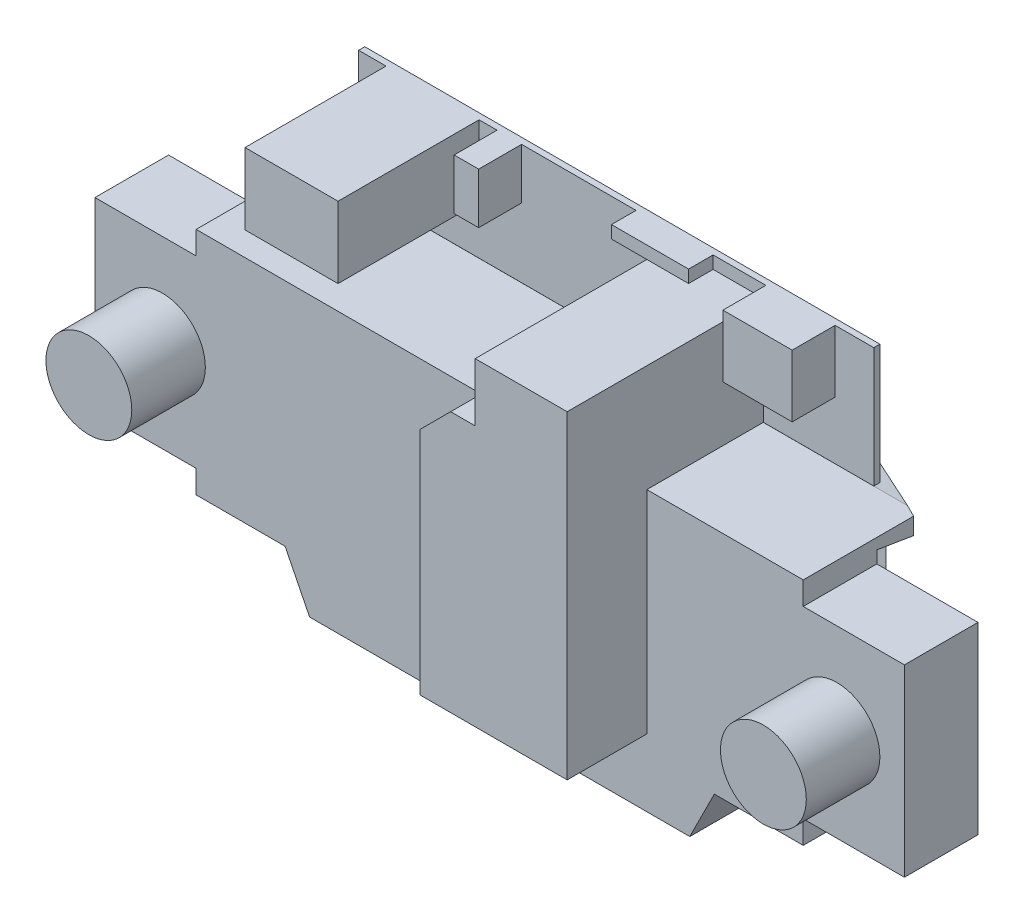
SolidWorks part; units mm, degrees
ref_plane "Front Plane" through (0, 0, 0) normal (0, 0, 1) x (1, 0, 0)
ref_plane "Top Plane" through (0, 0, 0) normal (0, 1, 0) x (1, 0, 0)
ref_plane "Right Plane" through (0, 0, 0) normal (1, 0, 0) x (0, 0, -1)
sketch "Sketch1" plane through (0, 0, 0) normal (0, 0, 1) x (1, 0, 0)
  line L1 (49.5, 0) -> (49.5, 18.75)
  line L2 (49.5, 18.75) -> (-49.5, 18.75)
  line L3 (-49.5, 18.75) -> (-49.5, -18.75)
  line L4 (-49.5, -18.75) -> (49.5, -18.75)
  line L5 (49.5, -18.75) -> (49.5, 0)
  dimension "D1" = 99
  dimension "D2" = 37.5
extrude "Boss-Extrude1" add sketch "Sketch1" along normal blind 25
ref_plane "Plane1" through (0, 0, 5) normal (0, 0, -1) x (-1, 0, 0)
sketch "Sketch2" plane through (0, 0, 5) normal (0, 0, -1) x (-1, 0, 0)
  line L0 (-49.5, 18.75) -> (49.5, 18.75) construction
  line L1 (-42, 18.75) -> (42, 18.75)
  line L3 (42, 18.75) -> (42, 38.2965)
  line L4 (42, 38.2965) -> (-42, 38.2965)
  line L5 (-42, 38.2965) -> (-42, 18.75)
  dimension "D1" = 7.5
  dimension "D2" = 7.5
  dimension "D3" = 84
extrude "Boss-Extrude2" add sketch "Sketch2" against normal blind 24
sketch "Sketch3" plane through (49.5, 0, 0) normal (1, 0, 0) x (0, 0, -1)
  line L0 (-25, -18.75) -> (-25, 18.75) construction
  line L1 (-25, 15) -> (-13, 15)
  line L2 (-25, 15) -> (-25, -15)
  line L3 (-25, -15) -> (-13, -15)
  line L4 (-13, 15) -> (-13, -15)
  dimension "D1" = 12
  dimension "D2" = 3.75
  dimension "D3" = 30
  dimension "D4" = 3.75
extrude "Boss-Extrude3" add sketch "Sketch3" along normal blind 16.5
sketch "Sketch4" plane through (-49.5, 0, 0) normal (-1, 0, 0) x (0, 0, 1)
  line L0 (25, 18.75) -> (25, -18.75) construction
  line L1 (25, 15) -> (13, 15)
  line L2 (25, 15) -> (25, -15)
  line L3 (25, -15) -> (13, -15)
  line L4 (13, 15) -> (13, -15)
  line L5 (25, 18.75) -> (0, 18.75) construction
  dimension "D1" = 30
  dimension "D2" = 3.75
  dimension "D3" = 3.75
  dimension "D4" = 12
extrude "Boss-Extrude4" add sketch "Sketch4" along normal blind 16.5
sketch "Sketch5" plane through (0, 0, 25) normal (0, 0, 1) x (1, 0, 0)
  line L0 (-49.5, -18.75) -> (49.5, -18.75) construction
  line L2 (0, -15.75) -> (0, 36.25)
  line L3 (0, 36.25) -> (24, 36.25)
  line L4 (24, -15.75) -> (24, 36.25)
  line L6 (24, -15.75) -> (0, -15.75)
  dimension "D1" = 52
  dimension "D2" = 24
  dimension "D3" = 3
extrude "Boss-Extrude5" add sketch "Sketch5" along normal blind 13
sketch "Sketch9" plane through (0, -18.75, 0) normal (0, -1, 0) x (1, 0, 0)
  line L0 (-49.5, 25) -> (49.5, 25) construction
  line L1 (-35, 25) -> (35, 25)
  line L2 (-35, 25) -> (-35, 15)
  line L3 (-35, 15) -> (35, 15)
  line L4 (35, 25) -> (35, 15)
  dimension "D1" = 10
  dimension "D2" = 70
  dimension "D3" = 14.5
  dimension "D4" = 14.5
extrude "Boss-Extrude6" add sketch "Sketch9" along normal blind 8
chamfer "Chamfer1" distance 8 distance2 4 2 edges at (-35, -26.75, 20) (35, -26.75, 20) first distance on face at (-35, -23.75, 21.25) first distance on face at (35, -23.75, 18.75)
sketch "Sketch10" plane through (0, 0, 25) normal (0, 0, 1) x (1, 0, 0)
  circle A0 centre (-55, 0) radius 7
  circle A1 centre (55, 0) radius 7
  dimension "D2" = 14
  dimension "D1" = 110
  dimension "D3" = 55
extrude "Boss-Extrude7" add sketch "Sketch10" along normal blind 12
sketch "Sketch11" plane through (0, 0, 0) normal (0, 0, -1) x (-1, 0, 0)
  circle A0 centre (-26, 7.5) radius 1
  circle A1 centre (26, 7.5) radius 1
  circle A2 centre (26, -7.5) radius 1
  circle A3 centre (-26, -7.5) radius 1
  dimension "D4" = 2
  dimension "D1" = 26
  dimension "D2" = 52
  dimension "D3" = 15
  dimension "D5" = 15
  dimension "D6" = 52
extrude "Cut-Extrude1" cut sketch "Sketch11" against normal blind 5
sketch "Sketch12" plane through (0, -18.75, 0) normal (0, -1, 0) x (1, 0, 0)
  line L0 (66, 13) -> (49.5, 13) construction
  line L1 (49.5, 7) -> (35.5, 0)
  line L2 (49.5, 7) -> (49.5, 0)
  line L3 (-49.5, 0) -> (-49.5, 7)
  line L4 (-42.503, 13.2061) -> (-42.503, 9.7979)
  line L5 (49.5, 25) -> (49.5, 0) construction
  line L6 (42.5, 9.7979) -> (32.9043, 5)
  line L7 (-49.5, 0) -> (49.5, 0) construction
  line L8 (-34.503, 13.2061) -> (-34.503, 7)
  line L9 (42.5, 13) -> (34.5, 13)
  line L10 (-49.5, 25) -> (-49.5, 0) construction
  line L11 (34.5, 13) -> (34.5, 7)
  line L12 (42.5, 13) -> (42.5, 9.7979)
  line L13 (-34.503, 13.2061) -> (-42.503, 13.2061)
  line L14 (49.5, 0) -> (35.5, 0)
  line L15 (-42.503, 9.7979) -> (-32.9073, 5)
  line L16 (-35.5, 0) -> (-49.5, 7)
  line L17 (32.9043, 5) -> (-32.9073, 5)
  line L18 (-35.5, 0) -> (-49.5, 0)
  line L19 (-49.5, 0) -> (-49.4472, 0.2465)
  line L21 (34.5, 7) -> (-34.503, 7)
  point P2 (0, 0)
  point P3 (0, 0)
  dimension "D1" = 14
  dimension "D2" = 7
  dimension "D3" = 5
  dimension "D4" = 9.5957
  dimension "D5" = 9.5957
  dimension "D6" = 8
  dimension "D7" = 6
  dimension "D8" = 42.503
  dimension "D9" = 13.2061
extrude "Cut-Extrude24" cut sketch "Sketch12" against normal blind 37.4999
sketch "Sketch13" plane through (0, 18.7499, 0) normal (0, -1, 0) x (1, 0, 0)
  line L0 (49.5, 7) -> (49.5, 0)
  line L1 (49.5, 0) -> (35.5, 0)
  line L2 (35.5, 0) -> (49.5, 7)
  line L3 (-35.5, 0) -> (-49.5, 0)
  line L4 (-49.5, 0) -> (-49.5, 7)
  line L5 (-49.5, 7) -> (-35.5, 0)
extrude "Cut-Extrude25" cut sketch "Sketch13" against normal up to next
sketch "Sketch14" plane through (-49.5, 0, 0) normal (-1, 0, 0) x (0, 0, 1)
  line L1 (13, 15.6699) -> (7, 15.6699)
  line L2 (2.5332, 15.25) -> (13, 16.9919)
  line L5 (7, -14.75) -> (2.5332, -10.75)
  line L6 (2.5332, -10.75) -> (2.5332, 15.25)
  line L7 (7, 18.75) -> (7, -18.75) construction
  line L8 (13, 15.6699) -> (13, 16.9919)
  line L9 (7, 15.6699) -> (7, -14.75)
  line L11 (0, 17.75) -> (0, 18.75)
  line L12 (6.0089, 18.75) -> (0, 17.75)
  line L14 (0, -13.25) -> (6.1418, -18.75)
  line L15 (0, 18.75) -> (6.0089, 18.75)
  line L16 (6.1418, -18.75) -> (0, -18.75)
  line L17 (0, -18.75) -> (0, -13.25)
  dimension "D5" = 26
  dimension "D6" = 4
  dimension "D7" = 31
  dimension "D8" = 1
extrude "Cut-Extrude26" cut sketch "Sketch14" against normal blind 99
sketch "Sketch15" plane through (-49.5, 0, 0) normal (-1, 0, 0) x (0, 0, 1)
  line L0 (7, -14.75) -> (13, -14.75)
  line L1 (13, 15.6699) -> (13, 15)
  line L13 (13, 16.9919) -> (13, 15.6699)
  line L14 (13, 15.6699) -> (7, 15.6699)
  line L15 (7, 15.6699) -> (7, -14.75)
  line L16 (7, -14.75) -> (7, -18.75)
  line L17 (7, -18.75) -> (25, -18.75)
  line L18 (25, -18.75) -> (25, -15)
  line L19 (25, -15) -> (13, -15)
  line L20 (13, -15) -> (13, 15)
  line L21 (13, 15) -> (25, 15)
  line L22 (25, 15) -> (25, 18.75)
  line L23 (25, 18.75) -> (7, 18.75)
  line L24 (7, 18.75) -> (7, 15.9934)
  line L25 (7, 15.9934) -> (13, 16.9919)
  line L27 (13, 15.6699) -> (7, 15.6699)
  line L28 (7, 15.6699) -> (7, -14.75)
  line L33 (13, -14.75) -> (13, 15)
  dimension "D1" = 0
extrude "Cut-Extrude27" cut sketch "Sketch15" against normal up to next
sketch "Sketch16" plane through (-34.503, 0, 0) normal (-1, 0, 0) x (0, 0, 1)
  line L0 (13, 15.6699) -> (13.2061, 15.6699)
  line L8 (13, 15.6699) -> (7, 15.6699)
  line L9 (7, 15.6699) -> (7, -18.75)
  line L10 (7, -18.75) -> (13.2061, -18.75)
  line L11 (13.2061, -18.75) -> (13.2061, 18.7499)
  line L12 (13.2061, 18.7499) -> (7, 18.7499)
  line L13 (7, 18.7499) -> (7, 15.9934)
  line L14 (7, 15.9934) -> (13, 16.9919)
  line L15 (13, 16.9919) -> (13, 15.6699)
  line L19 (13.2061, 15.6699) -> (13.2061, 18.7499)
  line L20 (13.2061, 18.7499) -> (7, 18.7499)
  line L21 (7, 18.7499) -> (7, 15.9934)
  line L22 (7, 15.9934) -> (13, 16.9919)
  line L23 (13, 16.9919) -> (13, 15.6699)
  dimension "D1" = 0
extrude "Cut-Extrude28" cut sketch "Sketch16" against normal up to surface (69.003 mm away) up to face at (34.5, 17.6213, 10)
sketch "Sketch18" plane through (49.5, 0, 0) normal (1, 0, 0) x (0, 0, -1)
  line L0 (-13, 15.6699) -> (-13, 15)
  line L1 (-7, -14.75) -> (-13, -14.75)
  line L13 (-7, -14.75) -> (-7, 15.6699)
  line L14 (-7, 15.6699) -> (-13, 15.6699)
  line L15 (-13, 15.6699) -> (-13, 16.9919)
  line L16 (-13, 16.9919) -> (-7, 15.9934)
  line L17 (-7, 15.9934) -> (-7, 18.75)
  line L18 (-7, 18.75) -> (-25, 18.75)
  line L19 (-25, 18.75) -> (-25, 15)
  line L20 (-25, 15) -> (-13, 15)
  line L21 (-13, 15) -> (-13, -15)
  line L22 (-13, -15) -> (-25, -15)
  line L23 (-25, -15) -> (-25, -18.75)
  line L24 (-25, -18.75) -> (-7, -18.75)
  line L25 (-7, -18.75) -> (-7, -14.75)
  line L26 (-7, -14.75) -> (-7, 15.6699)
  line L27 (-7, 15.6699) -> (-13, 15.6699)
  line L34 (-13, 15) -> (-13, -14.75)
  dimension "D1" = 0
extrude "Cut-Extrude29" cut sketch "Sketch18" against normal up to next
sketch "Sketch19" plane through (0, -18.75, 0) normal (0, -1, 0) x (1, 0, 0)
  line L0 (42.5, 13) -> (34.5, 13) construction
  line L1 (-34.503, 7) -> (34.5, 7)
  line L2 (-34.503, 7) -> (-34.503, 13)
  line L3 (-34.503, 13) -> (34.5, 13)
  line L4 (34.5, 7) -> (34.5, 13)
  line L5 (34.5, 13) -> (34.5, 7) construction
extrude "Cut-Extrude30" cut sketch "Sketch19" against normal blind 3
sketch "Sketch20" plane through (0, 0, 29) normal (0, 0, 1) x (1, 0, 0)
  line L0 (-42, 38.2965) -> (42, 38.2965) construction
  line L1 (3.2298, 36.25) -> (0, 36.25)
  line L2 (-37.5337, 38.2965) -> (-37.5337, 26.6597)
  line L3 (-37.5337, 26.6597) -> (-22.3637, 26.6597)
  line L4 (-22.3637, 38.2965) -> (-22.3637, 26.6597)
  line L5 (24, 36.25) -> (0, 36.25) construction
  line L7 (-19.4291, 38.2965) -> (-19.4291, 30.0174)
  line L8 (-19.4291, 30.0174) -> (-15.4315, 30.0174)
  line L9 (-15.4315, 38.2965) -> (-15.4315, 30.0174)
  line L11 (24.4025, 38.2965) -> (24.4025, 28.1577)
  line L12 (24.4025, 28.1577) -> (35.6958, 28.1577)
  line L13 (35.6958, 38.2965) -> (35.6958, 28.1577)
  line L15 (3.2298, 38.2965) -> (3.2298, 36.25)
  line L17 (15.803, 38.2965) -> (15.803, 36.25)
  line L18 (-42, 18.75) -> (-42, 38.2965)
  line L19 (-42, 38.2965) -> (-37.5337, 38.2965)
  line L20 (-22.3637, 38.2965) -> (-19.4291, 38.2965)
  line L21 (-15.4315, 38.2965) -> (3.2298, 38.2965)
  line L22 (24.4025, 38.2965) -> (15.803, 38.2965)
  line L23 (35.6958, 38.2965) -> (42, 38.2965)
  line L24 (42, 38.2965) -> (42, 18.75)
  line L25 (42, 18.75) -> (24, 18.75) construction
  line L26 (42, 38.2965) -> (42, 18.75) construction
  line L27 (42, 18.75) -> (24, 18.75)
  line L28 (24, 18.75) -> (24, 36.25)
  line L29 (24, 36.25) -> (15.803, 36.25)
  line L30 (0, 36.25) -> (0, 18.75)
  line L31 (0, 18.75) -> (-42, 18.75) construction
  line L32 (0, 18.75) -> (-42, 18.75)
extrude "Cut-Extrude32" cut sketch "Sketch20" against normal blind 23
sketch "Sketch21" plane through (0, 0, 29) normal (0, 0, 1) x (1, 0, 0)
  line L0 (-15.4315, 38.2965) -> (-19.4291, 38.2965) construction
  line L1 (-19.4291, 38.2965) -> (-19.4291, 30.0174) construction
  line L2 (-19.4291, 30.0174) -> (-15.4315, 30.0174) construction
  line L3 (-15.4315, 30.0174) -> (-15.4315, 38.2965) construction
  line L4 (35.6958, 38.2965) -> (24.4025, 38.2965) construction
  line L5 (24.4025, 38.2965) -> (24.4025, 28.1577) construction
  line L6 (24.4025, 28.1577) -> (35.6958, 28.1577) construction
  line L7 (35.6958, 28.1577) -> (35.6958, 38.2965) construction
  line L8 (-15.4315, 38.2965) -> (-19.4291, 38.2965)
  line L9 (-19.4291, 38.2965) -> (-19.4291, 30.0174)
  line L10 (-19.4291, 30.0174) -> (-15.4315, 30.0174)
  line L11 (-15.4315, 30.0174) -> (-15.4315, 38.2965)
  line L12 (35.6958, 38.2965) -> (24.4025, 38.2965)
  line L13 (24.4025, 38.2965) -> (24.4025, 28.1577)
  line L14 (24.4025, 28.1577) -> (35.6958, 28.1577)
  line L15 (35.6958, 28.1577) -> (35.6958, 38.2965)
extrude "Cut-Extrude33" cut sketch "Sketch21" against normal blind 16
sketch "Sketch22" plane through (0, 0, 29) normal (0, 0, 1) x (1, 0, 0)
  line L4 (3.2298, 36.25) -> (15.803, 36.25)
  line L5 (15.803, 36.25) -> (15.803, 38.2965)
  line L6 (15.803, 38.2965) -> (3.2298, 38.2965)
  line L7 (3.2298, 38.2965) -> (3.2298, 36.25)
  line L8 (3.2298, 36.25) -> (15.803, 36.25)
  line L9 (15.803, 36.25) -> (15.803, 38.2965)
  line L10 (15.803, 38.2965) -> (3.2298, 38.2965)
  line L11 (3.2298, 38.2965) -> (3.2298, 36.25)
  dimension "D1" = 0
extrude "Cut-Extrude34" cut sketch "Sketch22" against normal blind 19
sketch "Sketch23" plane through (0, 0, 38) normal (0, 0, 1) x (1, 0, 0)
  line L1 (0, 36.25) -> (0, -15.75) construction
  line L2 (0, 21.75) -> (5, 26.75)
  line L3 (5, 26.75) -> (9, 26.75)
  line L4 (9, 26.75) -> (9, 36.25)
  line L5 (24, 36.25) -> (0, 36.25) construction
  line L6 (9, 36.25) -> (0, 36.25)
  line L7 (0, 36.25) -> (0, 21.75)
  dimension "D2" = 5
  dimension "D3" = 5
  dimension "D4" = 4
extrude "Cut-Extrude35" cut sketch "Sketch23" against normal blind 32
